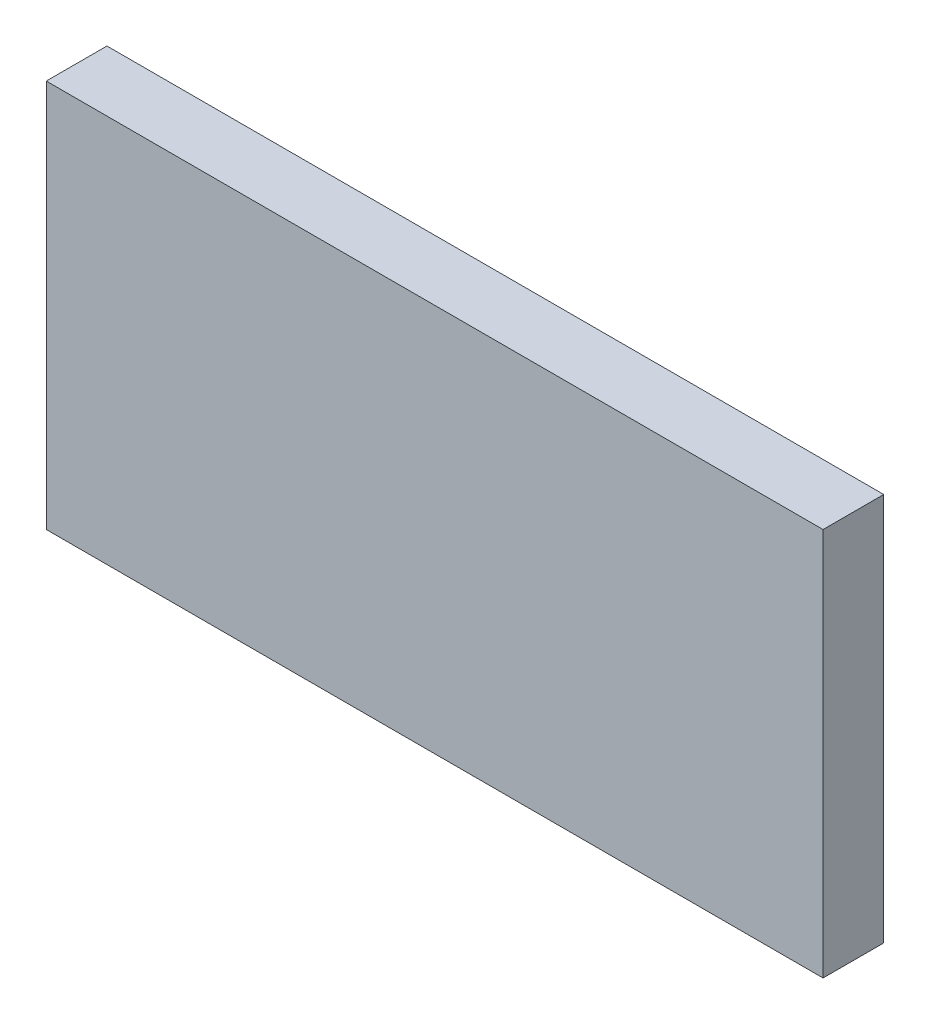
SolidWorks part; units mm, degrees
ref_plane "Front Plane" through (0, 0, 0) normal (0, 0, 1) x (1, 0, 0)
ref_plane "Top Plane" through (0, 0, 0) normal (0, 1, 0) x (1, 0, 0)
ref_plane "Right Plane" through (0, 0, 0) normal (1, 0, 0) x (0, 0, -1)
sketch "Sketch12" plane through (0, 0, 0) normal (0, 0, 1) x (1, 0, 0)
  line L1 (-32, 16) -> (32, 16)
  line L2 (-32, 16) -> (-32, -16)
  line L3 (-32, -16) -> (32, -16)
  line L4 (32, 16) -> (32, -16)
  line L5 (-32, 16) -> (32, -16) construction
  line L6 (-32, -16) -> (32, 16) construction
  point P0 (0, 0)
  dimension "D1" = 32
  dimension "D2" = 64
extrude "Boss-Extrude1" add sketch "Sketch12" along normal blind 5
